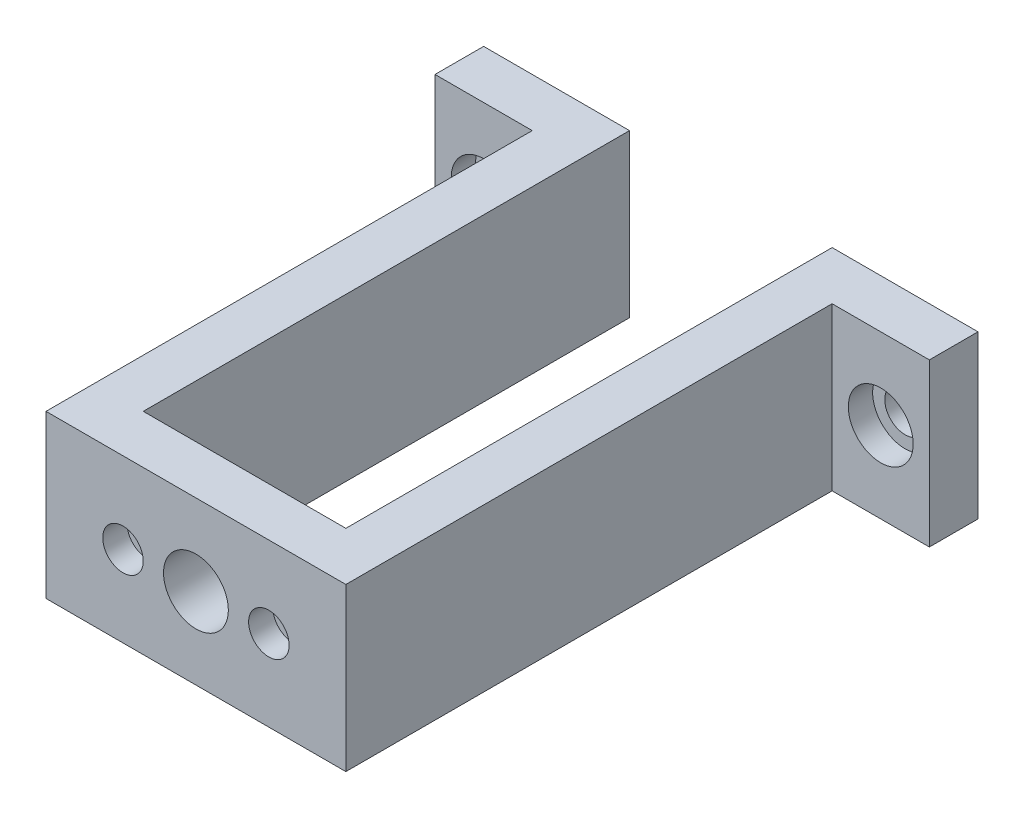
SolidWorks part; units mm, degrees
ref_plane "前视基准面" through (0, 0, 0) normal (0, 0, 1) x (1, 0, 0)
ref_plane "上视基准面" through (0, 0, 0) normal (0, 1, 0) x (1, 0, 0)
ref_plane "右视基准面" through (0, 0, 0) normal (1, 0, 0) x (0, 0, -1)
other "Configuration Table"
sketch "草图1" plane through (0, 0, 0) normal (0, 0, 1) x (1, 0, 0)
  line L9 (-12.5, 5) -> (0, 5)
  line L10 (-12.5, 5) -> (-12.5, -5)
  line L16 (-12.5, -5) -> (0, -5)
  line L17 (0, 5) -> (0, -5)
  dimension "D2" = 12.5
  dimension "D1" = 10
extrude "凸台-拉伸1" add sketch "草图1" along normal blind 3 contours L16 L17 L9 L10
sketch "草图2" plane through (0, 0, 3) normal (0, 0, 1) x (1, 0, 0)
  circle A0 centre (-10.75, 0) radius 0.85
  circle A1 centre (-1.75, 0) radius 0.85
  circle A2 centre (-1.75, 0) radius 1.25
  circle A3 centre (-10.75, 0) radius 1.25
  circle A4 centre (-6.25, 0) radius 2
  point P6 (0, 0)
  point P9 (0, 0)
  point P10 (0, 0)
  point P11 (0, 0)
  point P12 (0, 0)
  dimension "D1" = 1.7
  dimension "D2" = 2.5
  dimension "D3" = 4
extrude "切除-拉伸1" cut sketch "草图2" against normal through all contours A1 | A0 | A4
extrude "切除-拉伸2" cut sketch "草图2<3>" against normal blind 1.5 contours A2 | A3 | A4
sketch "草图2<3>" plane through (0, 0, 3) normal (0, 0, 1) x (1, 0, 0) same geometry as "草图2"
sketch "草图3" plane through (0, 0, 0) normal (0, 0, -1) x (-1, 0, 0)
  line L0 (0, 5) -> (0, -5) construction
  line L1 (0, 5) -> (-9, 5)
  line L2 (0, 5) -> (0, -5)
  line L3 (0, -5) -> (-9, -5)
  line L4 (-9, 5) -> (-9, -5)
  line L5 (12.5, 5) -> (12.5, -5) construction
  line L6 (12.5, 5) -> (21.5, 5)
  line L7 (12.5, 5) -> (12.5, -5)
  line L8 (12.5, -5) -> (21.5, -5)
  line L9 (21.5, 5) -> (21.5, -5)
  line L10 (12.5, -5) -> (0, -5) construction
  line L11 (12.5, 5) -> (0, 5) construction
  line L12 (-3, 5) -> (-3, -5)
  line L13 (15.5, 5) -> (15.5, -5)
  line L14 (-3, -4.0411) -> (0, -4.0411) construction
  line L15 (12.5, -4.0411) -> (15.5, -4.0411) construction
  line L16 (-9, 0) -> (-3, 0) construction
  line L17 (15.5, 0) -> (21.5, 0) construction
  circle A0 centre (-6, 0) radius 2
  circle A1 centre (-6, 0) radius 1.25
  circle A2 centre (18.5, 0) radius 2
  circle A3 centre (18.5, 0) radius 1.25
  line M13 (12.5, -5) -> (12.5, 5)
  line M15 (0, 5) -> (0, -5)
  dimension "D3" = 2.5
  dimension "D4" = 4
  dimension "D1" = 9
  dimension "D2" = 3
extrude "凸台-拉伸2" add sketch "草图3" along normal blind 30 separate body contours L6 L9 L8 L7 | L1 L4 L3 L2
extrude "凸台-拉伸3" add sketch "草图3<3>" against normal up to surface (3 mm away) contours L13 L6 L8 M13 | L1 L12 L3 M15 region at (1.5, 0, 0) region at (-14, 0, 0) up to face at (-0.5, 0, 3)
sketch "草图3<3>" plane through (0, 0, 0) normal (0, 0, -1) x (-1, 0, 0) same geometry as "草图3"
extrude "切除-拉伸3" cut sketch "草图3<4>" along normal offset from surface (27 mm away) 3 contours L12 L1 L4 L3 A0 | L6 L13 L8 L9 A2 | A0 A1 | A1 | A2 A3 | A3 region at (3.1166, 0, 0) region at (-18.5, 4.8834, 0) region at (7.9434, 0, 0) region at (6, 0, 0) region at (-16.5566, 0, 0) region at (-18.5, 0, 0) up to face at (4.5, 0, -30)
sketch "草图3<4>" plane through (0, 0, 0) normal (0, 0, -1) x (-1, 0, 0) same geometry as "草图3"
extrude "切除-拉伸4" cut sketch "草图3<5>" along normal through all contours A3 | A1 region at (6, 0, 0) region at (-18.5, 0, 0)
sketch "草图3<5>" plane through (0, 0, 0) normal (0, 0, -1) x (-1, 0, 0) same geometry as "草图3"
extrude "切除-拉伸5" cut sketch "草图3<6>" along normal blind 1.5 from surface contours A2 A3 | A0 A1 region at (7.9434, 0, 0) region at (-16.5566, 0, 0) starting at face at (-17.25, 0, -27)
sketch "草图3<6>" plane through (0, 0, 0) normal (0, 0, -1) x (-1, 0, 0) same geometry as "草图3"
